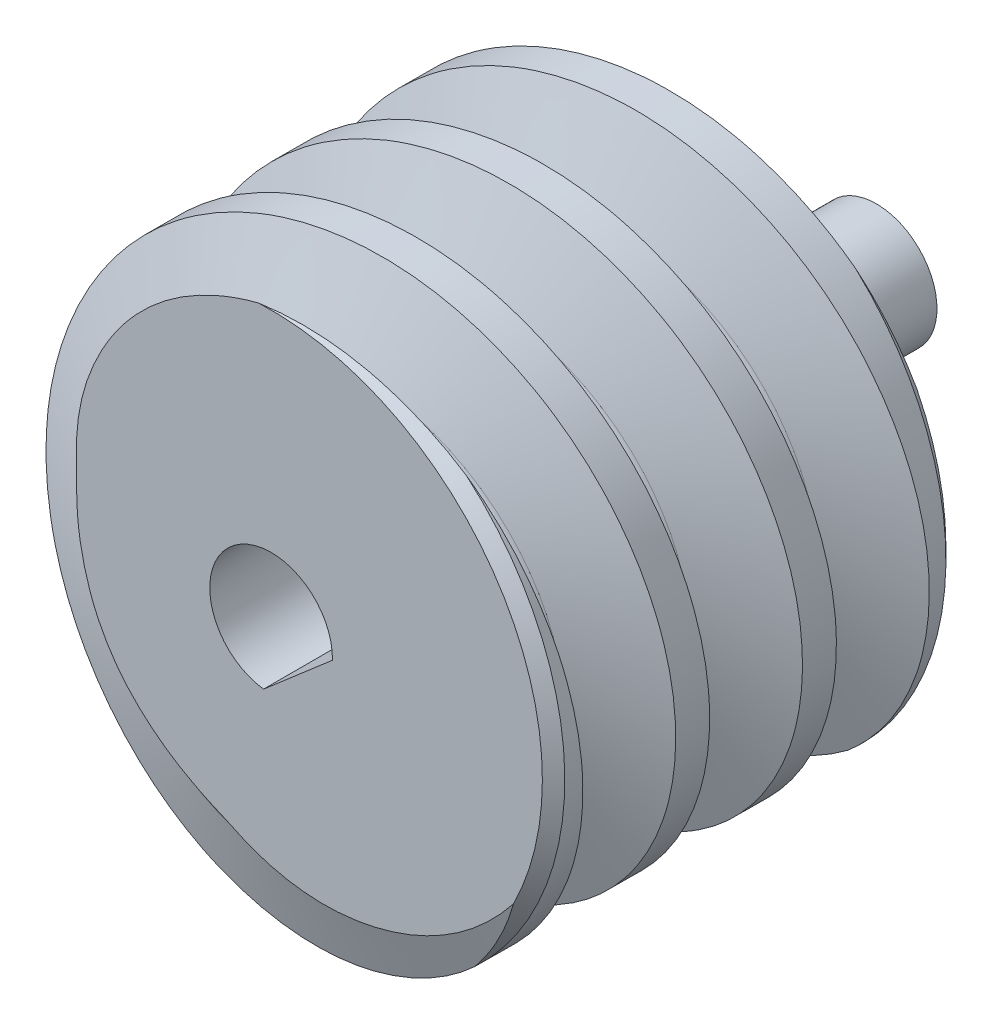
SolidWorks part; units mm, degrees
note: '?' marks a value the reader was unsure of. The reader was unsure of these and kept them because the rebuilt part matched: shared geometry of "Эскиз4<2>".
ref_plane "Спереди" through (0, 0, 0) normal (0, 0, 1) x (1, 0, 0)
ref_plane "Сверху" through (0, 0, 0) normal (0, 1, 0) x (1, 0, 0)
ref_plane "Справа" through (0, 0, 0) normal (1, 0, 0) x (0, 0, -1)
ref_axis "Ось1" through (0, 0, 22.8485) along (0, 0, -1)?
sketch "SketchRevolveWorm01" plane through (0, 0, 0) normal (1, 0, 0) x (0, 0, -1)
  line L0 (0, 0) -> (1, 0) construction
  line L1 (5, 0) -> (5, 6.722)
  line L2 (5, 6.722) -> (4.722, 7)
  line L3 (4.722, 7) -> (-4.722, 7)
  line L4 (-4.722, 7) -> (-5, 6.722)
  line L5 (-5, 6.722) -> (-5, 0)
  line L6 (-5, 0) -> (5, 0)
  dimension "ChamferX" = 0.278
  dimension "ChamferY" = 0.278
  dimension "OutsideDiameter" = 7
  dimension "WormLength" = 10
revolve "Worm01" add sketch "SketchRevolveWorm01" angle 360 about L0
ref_plane "HelixPlaneWorm01" through (0, 0, 9.4248) normal (0, 0, 1) x (1, 0, 0)
sketch "SketchHelixWorm01" plane through (0, 0, 9.4248) normal (0, 0, 1) x (1, 0, 0)
  circle A0 centre (0, 0) radius 6
  dimension "PitchDiameter" = 12
curve "GearHelixWorm01" pitch 3.1416 height 18.8496 turns 6
sketch "SketchToothWorm01" plane through (0, 0, 0) normal (0, 1, 0) x (1, 0, 0)
  line L0 (7.25, -8.1827) -> (4.9471, -9.0241)
  line L1 (4.75, -9.3058) -> (4.75, -9.5437)
  line L2 (4.9471, -9.8255) -> (7.25, -10.6669)
  line L3 (7.25, -10.6669) -> (7.25, -8.1827)
  arc A0 (4.9471, -9.0241) -> (4.75, -9.3058) centre (5.05, -9.3058) ccw
  arc A1 (4.75, -9.5437) -> (4.9471, -9.8255) centre (5.05, -9.5437) ccw
sweep "ToothCutWorm01" cut profiles "SketchToothWorm01" path "GearHelixWorm01"
sketch "BoreRevolveSketch" plane through (0, 0, 0) normal (1, 0, 0) x (0, 0, -1)
  line L0 (-5, 0) -> (5, 0)
  line L1 (5, 0) -> (5, 2.5)
  line L2 (5, 2.5) -> (-5, 2.5)
  line L3 (-5, 2.5) -> (-5, 0)
  dimension "TaperSide1" = 2.5
  dimension "TaperSide2" = 2.5
sketch "AuxiliarySketchWorm01" plane through (0, 0, 0) normal (0, 0, 1) x (1, 0, 0)
  circle A0 centre (0, 0) radius 6 construction
  dimension "PitchDiameter" = 12
sketch "Эскиз1" plane through (0, 0, -5) normal (0, 0, -1) x (-1, 0, 0)
  line L2 (-1.5196, -0.0357) -> (0.1866, -1.5085)
  line L3 (-1.5196, -0.0357) -> (0.1866, -1.5085)
  arc A2 (0.1866, -1.5085) -> (-1.5196, -0.0357) centre (0, 0) ccw
  arc A3 (0.1866, -1.5085) -> (-1.5196, -0.0357) centre (0, 0) ccw
  dimension "D1" = 0.05
extrude "Вырез-Вытянуть1" cut sketch "Эскиз1" against normal through all
ref_plane "Плоскость1" through (1.5196, -0.0357, -5) normal (-0.0235, -0.9997, 0) x (-0.9997, 0.0235, 0)
sketch "Эскиз4" plane through (0, 0, -5) normal (0, 0, -1) x (-1, 0, 0)
  circle A0 centre (0, 0) radius 2.5
  circle A1 centre (0, 0) radius 1.5
  line M3 (0.1866, -1.5085) -> (-1.5196, -0.0357)
extrude "Бобышка-Вытянуть2" add sketch "Эскиз4" along normal blind 1
extrude "Бобышка-Вытянуть3" add sketch "Эскиз4<2>" along normal blind 6 from surface at -1 contours A1 M3 | A1 M3
sketch "Эскиз4<2>" plane through (0, 0, -5) normal (0, 0, -1) x (-1, 0, 0) same geometry as "Эскиз4"
